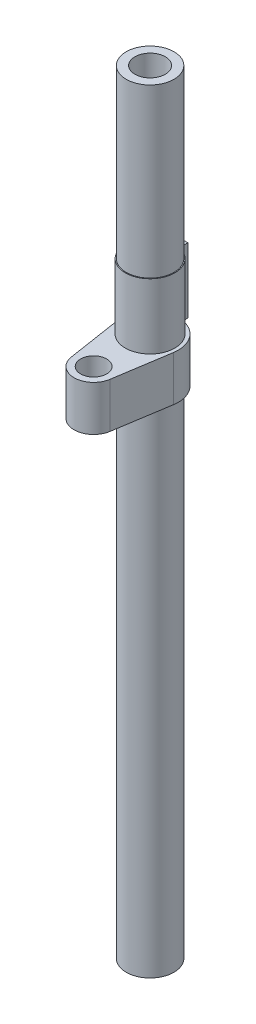
SolidWorks part; units mm, degrees
ref_plane "Ön Düzlem" through (0, 0, 0) normal (0, 0, 1) x (1, 0, 0)
ref_plane "Üst Düzlem" through (0, 0, 0) normal (0, 1, 0) x (1, 0, 0)
ref_plane "Sağ Düzlem" through (0, 0, 0) normal (1, 0, 0) x (0, 0, -1)
sketch "Sketch1" plane through (0, 0, 0) normal (0, 1, 0) x (1, 0, 0)
  circle A0 centre (0, 0) radius 2.75
  dimension "D1" = 5.5
extrude "Boss-Extrude1" add sketch "Sketch1" along normal blind 87.927
sketch "Sketch2" plane through (0, 0, 0) normal (0, -1, 0) x (1, 0, 0)
  circle A0 centre (0, 0) radius 1.75
  dimension "D1" = 3.5
extrude "Cut-Extrude1" cut sketch "Sketch2" against normal blind 8.9
extrude "Cut-Extrude2" cut sketch "Sketch2<2>" along normal blind 8.9 from surface starting at face at (0, 87.927, 2.75)
sketch "Sketch2<2>" plane through (0, 0, 0) normal (0, -1, 0) x (1, 0, 0) same geometry as "Sketch2"
ref_plane "Plane1" through (-2.75, 0, 0) normal (-1, 0, 0) x (0, 0, 1)
sketch "Sketch3" plane through (-2.75, 0, 0) normal (-1, 0, 0) x (0, 0, 1)
  line L0 (0, 4.677) -> (0, 0) construction
  line L1 (2.75, 87.927) -> (-2.75, 87.927) construction
  circle A0 centre (0, 4.677) radius 1.75
  circle A1 centre (0, 82.177) radius 1.75
  dimension "D2" = 3.5
  dimension "D1" = 4.677
  dimension "D3" = 5.75
extrude "Cut-Extrude3" cut sketch "Sketch3" against normal up to surface (2.75 mm away) up to face at (0, 79.027, 1.75)
ref_plane "Plane2" through (0, 68.677, 0) normal (0, 1, 0) x (1, 0, 0)
sketch "Sketch4" plane through (0, 68.677, 0) normal (0, 1, 0) x (1, 0, 0)
  line L0 (-0.75, 2.9047) -> (-0.75, 3.9047) construction
  line L1 (0.75, 2.9047) -> (0.75, 3.9047) construction
  line L2 (-0.75, 3.4047) -> (0.75, 3.4047) construction
  line L3 (-0.75, 3.9047) -> (0.75, 3.9047) construction
  line L4 (0.6, 2.7861) -> (0.6, 3.7547)
  line L5 (-0.6, 3.7547) -> (0.6, 3.7547)
  line L6 (-0.6, 2.7861) -> (-0.6, 3.7547)
  arc A0 (-0.75, 2.9047) -> (0.75, 2.9047) centre (0, 0) ccw construction
  arc A1 (-0.6, 2.7861) -> (0.6, 2.7861) centre (0, 0) ccw
  circle A2 centre (0, 0) radius 2.75 construction
  circle A3 centre (0, 0) radius 2.75
  point P9 (0, 3.4047)
  dimension "D1" = 6
  dimension "D2" = 1.5
  dimension "D3" = 1
  dimension "D4" = 0.15
extrude "Boss-Extrude2" add sketch "Sketch4" against normal blind 7.5
sketch "Sketch5" plane through (0, 61.177, 0) normal (0, -1, 0) x (1, 0, 0)
  line L0 (-3.2113, 0.5) -> (-2.2232, 6.8462)
  line L1 (2.2232, 6.8462) -> (3.2113, 0.5)
  arc A0 (2.2232, 6.8462) -> (-2.2232, 6.8462) centre (0, 6.5) ccw
  arc A1 (-3.2113, 0.5) -> (3.2113, 0.5) centre (0, 0) ccw
  circle A2 centre (0, 6.5) radius 1.5
  circle A3 centre (0, 0) radius 2.75 construction
  circle A4 centre (0, 0) radius 2.75
  dimension "D1" = 4.5
  dimension "D3" = 6.5
  dimension "D4" = 3
  dimension "D2" = 6.5
extrude "Boss-Extrude3" add sketch "Sketch5" along normal blind 5.2
sketch "Sketch6" plane through (0, 0, 0) normal (0, 1, 0) x (1, 0, 0)
  circle A0 centre (0, 0) radius 2.75
  circle A1 centre (0, 0) radius 1.75
  circle A2 centre (0, 0) radius 2.75 construction
extrude "Boss-Extrude5" add sketch "Sketch6" against normal blind 1.1
sketch "Sketch7" plane through (0, 79.027, 0) normal (0, 1, 0) x (1, 0, 0)
  circle A1 centre (0, 0) radius 1.75
  circle A2 centre (0, 0) radius 1.75
  dimension "D1" = 0
extrude "Boss-Extrude6" add sketch "Sketch7" along normal blind 0.4
sketch "Sketch8" plane through (0, 8.9, 0) normal (0, -1, 0) x (1, 0, 0)
  circle A1 centre (0, 0) radius 1.75
  circle A2 centre (0, 0) radius 1.75
  dimension "D1" = 0
extrude "Boss-Extrude7" add sketch "Sketch8" along normal blind 1.473
